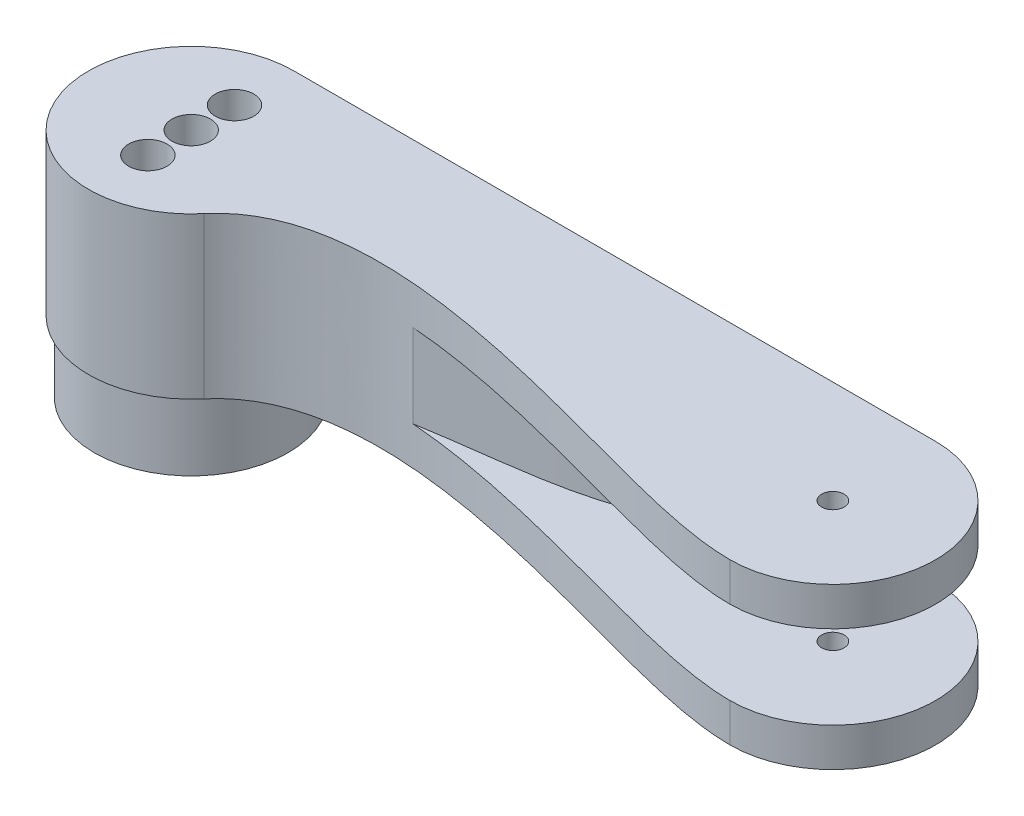
SolidWorks part; units mm, degrees
material "PLA"
ref_plane "Front Plane" through (0, 0, 0) normal (0, 0, 1) x (1, 0, 0)
ref_plane "Top Plane" through (0, 0, 0) normal (0, 1, 0) x (1, 0, 0)
ref_plane "Right Plane" through (0, 0, 0) normal (1, 0, 0) x (0, 0, -1)
sketch "Sketch1" plane through (0, 0, 0) normal (0, 1, 0) x (1, 0, 0)
  line L0 (-50, 0) -> (50, 0) construction
  line L1 (-50, 16) -> (50, 16)
  line L2 (-50, -16) -> (50, -16)
  arc A0 (-50, 16) -> (-50, -16) centre (-50, 0) ccw
  arc A1 (50, -16) -> (50, 16) centre (50, 0) ccw
  point P3 (0, 0)
  dimension "D1" = 16
  dimension "D2" = 100
extrude "Boss-Extrude1" add sketch "Sketch1" along normal blind 6
sketch "Sketch3" plane through (0, 0, 0) normal (0, -1, 0) x (1, 0, 0)
  circle A0 centre (50, 0) radius 1.75
  dimension "D1" = 3.5
extrude "Cut-Extrude2" cut sketch "Sketch3" against normal through all
sketch "Sketch4" plane through (0, 6, 0) normal (0, 1, 0) x (1, 0, 0)
  line L0 (-50, 16) -> (30, 16)
  line L1 (-50, 16) -> (50, 16) construction
  line L4 (-34.2857, -16) -> (-50, -16)
  line L5 (-50, -16) -> (50, -16) construction
  arc A0 (-50, 16) -> (-50, -16) centre (-50, 0) ccw
  arc A1 (-50, 16) -> (-50, -16) centre (-50, 0) ccw construction
  spline S0 degree 3 poles (30, 16) (21.9929, -10.8622) (-23.6763, 6.1181) (-34.2857, -16) knots 0 0 0 0 1 1 1 1
  dimension "D1" = 80
extrude "Boss-Extrude2" add sketch "Sketch4" along normal blind 13
sketch "Sketch5" plane through (0, 19, 0) normal (0, 1, 0) x (1, 0, 0)
  line L0 (-50, 0) -> (50, 0) construction
  line L1 (-50, 16) -> (50, 16)
  line L2 (-50, -16) -> (50, -16)
  arc A0 (-50, 16) -> (-50, -16) centre (-50, 0) ccw
  arc A1 (50, -16) -> (50, 16) centre (50, 0) ccw
  point P4 (0, 0)
  dimension "D1" = 16
extrude "Boss-Extrude3" add sketch "Sketch5" along normal blind 6
sketch "Sketch6" plane through (0, 25, 0) normal (0, 1, 0) x (1, 0, 0)
  circle A0 centre (50, 0) radius 1.75
  dimension "D1" = 3.5
extrude "Cut-Extrude3" cut sketch "Sketch6" against normal up to next
sketch "Sketch7" plane through (0, 25, 0) normal (0, 1, 0) x (1, 0, 0)
  line L0 (0, -3.3) -> (0, 3.3) construction
  line L1 (-50, -16) -> (50, -16)
  circle A0 centre (-50, 0) radius 16
  circle A1 centre (50, 0) radius 16
  spline S0 degree 3 poles (-37.7313, -10.2703) (-30.3326, -1.4318) (6.0504, -3.3646) (38.5122, -16) (50, -16) knots 0 0 0 0 0.426661 1 1 1 1
  line M5 (-50, -16) -> (50, -16)
extrude "Cut-Extrude4" cut sketch "Sketch7" against normal up to next contours S0 A0 M5 region at (-6.9153, 25, 11.0131)
sketch "Sketch8" plane through (0, 0, 0) normal (0, -1, 0) x (1, 0, 0)
  circle A1 centre (-50, 0) radius 15.1
  dimension "D1" = 30.2
extrude "Boss-Extrude4" add sketch "Sketch8" along normal blind 11
sketch "Sketch9" plane through (0, -11, 0) normal (0, -1, 0) x (1, 0, 0)
  circle A0 centre (-50, 0) radius 6.75 construction
  circle A1 centre (-50, 6.75) radius 1.75
  circle A2 centre (-50, -6.75) radius 1.75
  arc A3 (-50, 16) -> (-50, -16) centre (-50, 0) ccw construction
  point P6 (-50, 0)
  dimension "D1" = 13.5
  dimension "D2" = 3.5
extrude "Cut-Extrude5" cut sketch "Sketch9" against normal blind 10
sketch "Sketch11" plane through (0, -11, 0) normal (0, -1, 0) x (1, 0, 0)
  circle A0 centre (-50, 0) radius 3
  dimension "D1" = 6
extrude "Cut-Extrude6" cut sketch "Sketch11" against normal up to next and the other way through all
sketch "Sketch12" plane through (0, -1, 0) normal (0, -1, 0) x (1, 0, 0)
  circle A0 centre (-50, 0) radius 6.75 construction
  circle A1 centre (-50, 6.75) radius 3
  circle A2 centre (-50, -6.75) radius 3
  circle A3 centre (-50, 6.75) radius 1.75 construction
  dimension "D1" = 6
  dimension "D3" = 13.5
  dimension "D2" = 2
extrude "Cut-Extrude7" cut sketch "Sketch12" against normal up to next
equation "\"Length\"= 100mm"
equation "\"Radius\"= 14.25mm"
equation "\"Thick\"= 12mm"
equation "\"D1@Sketch1\"=16"
equation "\"D2@Sketch1\" = \"Length\""
equation "\"D1@Boss-Extrude1\"= \"Thick\""
equation "\"D1@Sketch4\"=\"Length\"*0.8"
equation "\"D1@Sketch5\"=16"
equation "\"D1@Boss-Extrude4\"=\"Thick\"-1"
